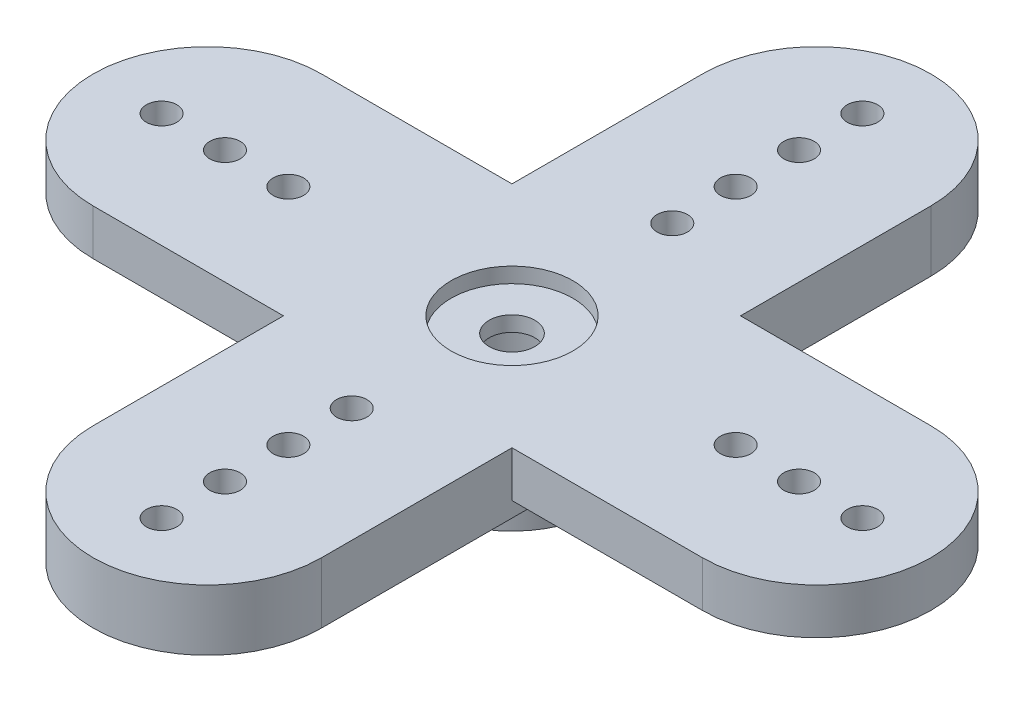
SolidWorks part; units mm, degrees
ref_plane "Front Plane" through (0, 0, 0) normal (0, 0, 1) x (1, 0, 0)
ref_plane "Top Plane" through (0, 0, 0) normal (0, 1, 0) x (1, 0, 0)
ref_plane "Right Plane" through (0, 0, 0) normal (1, 0, 0) x (0, 0, -1)
sketch "Sketch1" plane through (0, 0, 0) normal (0, 1, 0) x (1, 0, 0)
  line L0 (5.9531, 15.875) -> (5.9531, 5.9521)
  line L1 (-5.9531, 15.875) -> (-5.9531, 5.9521)
  line L2 (0, -1000) -> (0, 49000) construction
  line L3 (-1000, 0) -> (49000, 0) construction
  line L4 (15.876, -5.9541) -> (5.9531, -5.9541)
  line L5 (15.876, 5.9521) -> (5.9531, 5.9521)
  line L6 (-5.9531, -5.9541) -> (-5.9531, -15.875)
  line L7 (5.9531, -5.9541) -> (5.9531, -15.875)
  line L8 (-5.9531, 5.9521) -> (-15.874, 5.9521)
  line L9 (-5.9531, -5.9541) -> (-15.874, -5.9541)
  arc A0 (-5.9531, 15.875) -> (5.9531, 15.875) centre (0, 15.875) cw
  arc A1 (-5.9531, -15.875) -> (5.9531, -15.875) centre (0, -15.875) ccw
  arc A2 (15.876, 5.9521) -> (15.876, -5.9541) centre (15.876, -0.001) cw
  arc A3 (-15.874, 5.9521) -> (-15.874, -5.9541) centre (-15.874, -0.001) ccw
  circle A4 centre (-18.2562, 0) radius 0.7937
  circle A5 centre (0, 18.2563) radius 0.7937
  circle A6 centre (18.2562, 0) radius 0.7937
  circle A7 centre (0, -18.2562) radius 0.7938
  circle A8 centre (0, 0) radius 1.1906
  circle A9 centre (0, 14.9543) radius 0.7937
  circle A10 centre (0, 11.6523) radius 0.7937
  circle A11 centre (14.9543, 0) radius 0.7937
  circle A12 centre (11.6523, 0) radius 0.7937
  circle A13 centre (0, -14.9543) radius 0.7937
  circle A14 centre (0, -11.6523) radius 0.7937
  circle A15 centre (-14.9543, 0) radius 0.7937
  circle A16 centre (-11.6523, 0) radius 0.7937
  circle A17 centre (0, 8.3503) radius 0.7937
  circle A18 centre (0, -8.3503) radius 0.7937
  dimension "D3" = 5.9531
  dimension "D4" = 2
  dimension "D6" = 1.5875
  dimension "D9" = 2.3813
  dimension "D1" = 15.875
  dimension "D2" = 15.875
  dimension "D5" = 15.876
  dimension "D7" = 18.2562
  dimension "D10" = 3
  dimension "D12" = 2
  dimension "D13" = 2
  dimension "D8" = 4
  dimension "D11" = 4
extrude "Boss-Extrude1" add sketch "Sketch1" along normal blind 3.175
sketch "Sketch3" plane through (0, 0, 0) normal (0, -1, 0) x (1, 0, 0)
  line L0 (5.9531, -5.9521) -> (5.9531, 5.9541)
  line L1 (15.876, -5.9521) -> (5.9531, -5.9521)
  line L2 (15.876, 5.9541) -> (5.9531, 5.9541)
  line L4 (0, -11.6523) -> (0, 0.0102) construction
  line L5 (-15.876, 5.9541) -> (-5.9531, 5.9541)
  line L6 (-15.876, -5.9521) -> (-5.9531, -5.9521)
  line L7 (-5.9531, -5.9521) -> (-5.9531, 5.9541)
  arc A1 (15.876, -5.9521) -> (15.876, 5.9541) centre (15.876, 0.001) ccw
  arc A2 (-15.876, -5.9521) -> (-15.876, 5.9541) centre (-15.876, 0.001) cw
  point P17 (17.5951, -23.6079)
extrude "Cut-Extrude1" cut sketch "Sketch3" against normal blind 0.7937
sketch "Sketch4" plane through (0, 3.175, 0) normal (0, 1, 0) x (1, 0, 0)
  circle A0 centre (0, 0) radius 3.175
extrude "Cut-Extrude2" cut sketch "Sketch4" against normal blind 0.7937
sketch "Sketch5" plane through (0, 0, 0) normal (0, -1, 0) x (1, 0, 0)
  circle A0 centre (0, 0) radius 4.7625
  circle A1 centre (0, 0) radius 3.048
extrude "Boss-Extrude2" add sketch "Sketch5" along normal blind 3.175 contours A1 | A0
sketch "Sketch6" plane through (0, 0, 0) normal (0, -1, 0) x (1, 0, 0)
  circle A0 centre (0, 0) radius 3.048
extrude "Cut-Extrude3" cut sketch "Sketch6" against normal blind 1.5875
